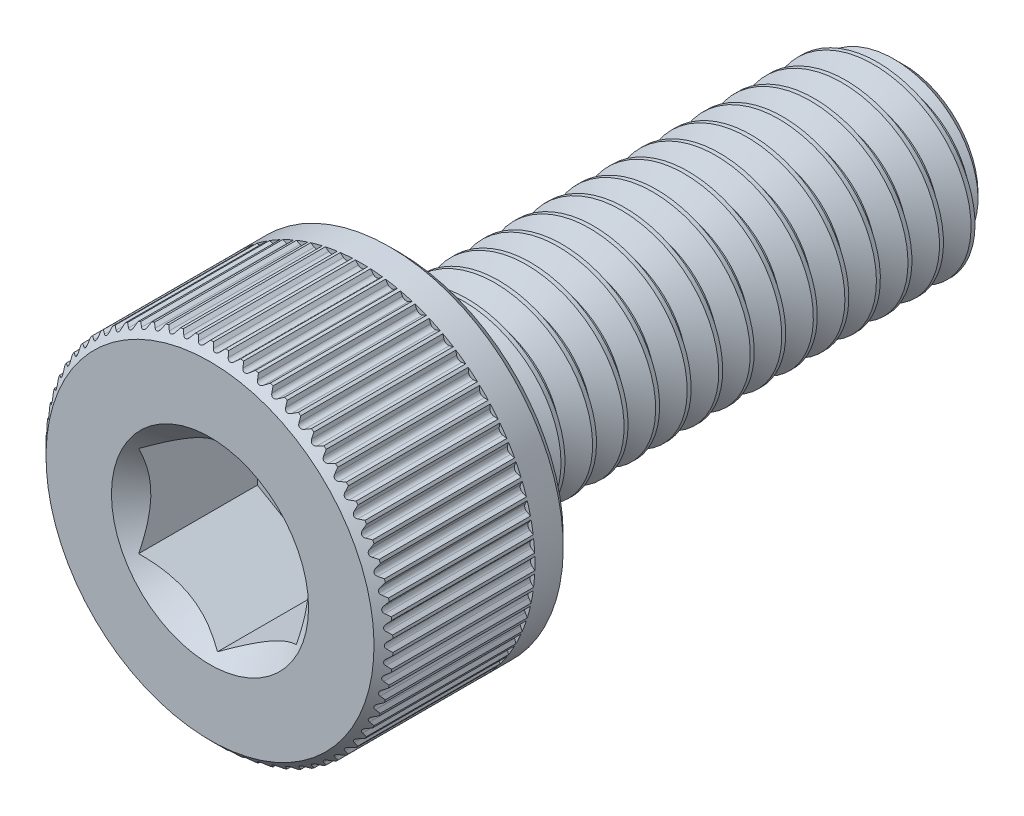
SolidWorks part; units mm, degrees
ref_plane "Front Plane" through (0, 0, 0) normal (0, 0, 1) x (1, 0, 0)
ref_plane "Top Plane" through (0, 0, 0) normal (0, 1, 0) x (1, 0, 0)
ref_plane "Right Plane" through (0, 0, 0) normal (1, 0, 0) x (0, 0, -1)
sketch "Sketch1" plane through (0, 0, 0) normal (1, 0, 0) x (0, 0, -1)
  line L0 (-5.5, 0) -> (5.5, 0) construction
  line L1 (5.5, 0) -> (5.5, 1.1752) construction
  line L2 (5.5, 1.1752) -> (5.1752, 1.5) construction
  line L3 (5.1752, 1.5) -> (5.125, 1.5) construction
  line L4 (5.125, 1.5) -> (-2.5, 1.5) construction
  line L5 (-2.5, 1.5) -> (-2.5, 2.75) construction
  line L6 (-2.5, 2.75) -> (-5.5, 2.75) construction
  line L7 (-5.5, 2.75) -> (-5.5, 0) construction
  line L8 (5.5, 1.1752) -> (5.5, 1.5) construction
  line L9 (5.4688, 1.5541) -> (5.7188, 1.1211) construction
  line L10 (5.7188, 1.1211) -> (5.9688, 1.5541) construction
  line L11 (5.9688, 1.5541) -> (5.4688, 1.5541) construction
  line L12 (5.7188, 1.5541) -> (5.7188, 1.5) construction
  line L13 (5.7188, 1.1211) -> (5.7188, 1.1752) construction
  line L14 (5.6875, 1.1752) -> (5.75, 1.1752) construction
  line L15 (5.5, 1.5) -> (5.9375, 1.5) construction
  line L16 (5.4844, 1.5271) -> (5.9531, 1.5271) construction
  line L17 (5.5, 0) -> (5.5, -1.5) construction
  line L18 (-2.65, 2.75) -> (-2.5, 2.6) construction
  line L19 (-5.35, 2.75) -> (-5.5, 2.6) construction
  line L20 (-2.5, 1.5) -> (-2.5, 0) construction
  line L21 (-2.5, 0.75) -> (0.1667, 0.75) construction
  line L22 (0.1667, 0.75) -> (2.8333, 0.75) construction
  line L23 (2.8333, 0.75) -> (5.5, 0.75) construction
  line L24 (0.1667, 0.75) -> (0.1667, 1.5) construction
  line L25 (0.1667, 1.5) -> (0.1667, 2.75) construction
  line L26 (2.8333, 0.75) -> (2.8333, 2.75) construction
  point P0 (-5.5, 1.25)
  point P3 (4.25, 1.5)
  point P4 (0, 0)
  point P18 (2.8333, 1.5)
  point P22 (5.7188, 1.1752)
  point P24 (5.125, 1.5)
  point P25 (5.7188, 1.5)
  point P28 (5.7188, 1.5271)
  point P29 (4.25, -1.5)
  point P30 (0.1667, 1.5)
  point P31 (-4, 2.75)
  point P37 (-3.025, 2.75)
  point P38 (-5.275, 2.75)
  point P45 (0.1667, 0.75)
  point P46 (2.8333, 0.75)
  dimension "D2" = 0.0625
  dimension "D7" = 0.15
  dimension "D8" = 0.15
  dimension "D9" = 0.15
  dimension "D10" = 0.075
  dimension "D11" = 0.375
  dimension "Drive Size" = 2.5
  dimension "Head Diameter" = 5.5
  dimension "Head Height" = 3
  dimension "Thread Pitch" = 0.5
  dimension "Thread Size" = 3
  dimension "Length" = 8
  dimension "D12" = 0.375
  dimension "D4" = 1.25
  dimension "D3" = 45
sketch "Sketch2" plane through (0, 0, 0) normal (1, 0, 0) x (0, 0, -1)
  line L0 (-5.5, 0) -> (-5.5, 2.6)
  line L1 (-5.35, 2.75) -> (-2.65, 2.75)
  line L2 (-2.5, 2.6) -> (-2.5, 1.65)
  line L4 (5.1752, 1.5) -> (5.5, 1.1752)
  line L5 (5.5, 1.1752) -> (5.5, 0)
  line L6 (-2.5, 2.75) -> (-5.5, 2.75) construction
  line L7 (5.5, 0) -> (-5.5, 0)
  line L8 (-5.35, 2.75) -> (-5.5, 2.6) construction
  line L10 (-5.35, 2.75) -> (-5.5, 2.6)
  line L14 (-2.65, 2.75) -> (-2.5, 2.6) construction
  line L16 (-2.65, 2.75) -> (-2.5, 2.6)
  line L17 (-2.5, 1.5) -> (-2.5, 2.75) construction
  line L19 (-2.35, 1.5) -> (5.1752, 1.5)
  line L20 (5.125, 1.5) -> (-2.5, 1.5) construction
  arc A1 (-2.5, 1.65) -> (-2.35, 1.5) centre (-2.35, 1.65) ccw
revolve "Revolve1" add sketch "Sketch2" angle 360 about L7
sketch "Sketch3" plane through (0, 0, 5.5) normal (0, 0, 1) x (1, 0, 0)
  line L1 (1.25, -0.7217) -> (1.25, 0.7217)
  line L2 (1.25, 0.7217) -> (0, 1.4434)
  line L3 (0, 1.4434) -> (-1.25, 0.7217)
  line L4 (-1.25, 0.7217) -> (-1.25, -0.7217)
  line L5 (-1.25, -0.7217) -> (0, -1.4434)
  line L6 (0, -1.4434) -> (1.25, -0.7217)
  circle A0 centre (0, 0) radius 1.25 construction
  circle A1 centre (0, 0) radius 2.75 construction
  circle A2 centre (0, 0) radius 2.75 construction
  circle A3 centre (0, 0) radius 1.4434 construction
  point P13 (0, 0)
extrude "Cut-Extrude1" cut sketch "Sketch3" against normal offset from surface (2 mm away) 1 up to face at (0, 2.6, 2.5)
sketch "Sketch4" plane through (0, 0, 5.5) normal (0, 0, 1) x (1, 0, 0)
  circle A0 centre (0, 0) radius 1.5625
  dimension "D1" = 3.125
extrude "Cut-Extrude2" cut sketch "Sketch4" against normal up to vertex (1.5 mm away) draft 45 up to point (0, 2.75, 4)
sketch "Sketch11" plane through (0, 0, 0) normal (1, 0, 0) x (0, 0, -1)
  line L0 (-5.5, 0) -> (5.5, 0) construction
  line L1 (-5.5, 0) -> (5.5, 0) construction
  line L2 (-1, 0) -> (-1, 1.5) construction
  line L3 (5.125, 1.5) -> (-2.5, 1.5) construction
  line L4 (4, 0) -> (4, 1.5) construction
  line L6 (5.5, 1.1752) -> (5.5, 1.5) construction
  point P2 (-1, 0)
  point P3 (4, 0)
  dimension "D1" = 1.5
  dimension "D2" = 1.5
sketch "Sketch6" plane through (0, 0, -5.5) normal (0, 0, -1) x (-1, 0, 0)
  circle A0 centre (0, 0) radius 1.5
curve "Helix/Spiral1" pitch 0.5 height 8.5 radius 1.5 centre (0, 0, -5.5) axis (0, 0, 1) start towards (0, 1, 0)
sketch "Sketch10" plane through (0, 0, 0) normal (1, 0, 0) x (0, 0, -1)
  line L0 (-2.35, -2.75) -> (-2.35, 2.75)
  line L5 (-5.5, 0) -> (5.5, 0) construction
  line L6 (-2.35, 1.5) -> (-2.35, -1.5) construction
  point P3 (-2.35, 0)
split "Split1" trim tools "Sketch10" bodies to split 106 resulting bodies 114 115
sketch "Sketch7" plane through (0, 0, 0) normal (1, 0, 0) x (0, 0, -1)
  line L0 (5.4844, 1.5271) -> (5.9531, 1.5271)
  line L1 (5.9531, 1.5271) -> (5.75, 1.1752)
  line L2 (5.75, 1.1752) -> (5.6875, 1.1752)
  line L3 (5.6875, 1.1752) -> (5.4844, 1.5271)
sweep "Cut-Sweep1" cut profiles "Sketch7" path "Helix/Spiral1" align with end faces yes
sketch "Sketch8" plane through (0, 0, 0) normal (1, 0, 0) x (0, 0, -1)
  line L0 (-2.5, 0) -> (-2.5, 1.5)
  line L1 (-2.35, -1.5) -> (-2.35, 1.5) construction
  line L2 (-2.5, 1.5) -> (-2.35, 1.5)
  line L4 (-2.35, 1.5) -> (-1.484, 0)
  line L5 (-1.484, 0) -> (-2.5, 0)
  line L6 (5.125, 1.5) -> (-2.5, 1.5) construction
  line L7 (-5.5, 0) -> (5.5, 0) construction
  dimension "D1" = 60
revolve "Revolve2" add sketch "Sketch8" angle 360 about L5
ref_plane "Plane1" through (0, 0, 5.5) normal (0, 0, 1) x (1, 0, 0)
sketch "Sketch12" plane through (0, 0, 5.5) normal (0, 0, 1) x (1, 0, 0)
  line L0 (0, 0) -> (0.096, 2.7483) construction
  line L1 (0, 0) -> (-0.096, 2.7483) construction
  line L2 (0, 2.6812) -> (0, 2.8187) construction
  line L3 (-0.1664, 2.8187) -> (0.1664, 2.8187)
  line L4 (-0.1664, 2.8187) -> (-0.0493, 2.7017)
  line L5 (0.0493, 2.7017) -> (0.1664, 2.8187)
  circle A0 centre (0, 0) radius 2.75 construction
  arc A1 (-0.0493, 2.7017) -> (0.0493, 2.7017) centre (0, 2.751) ccw
  point P9 (0, 2.8187)
  point P13 (0, 2.75)
  dimension "D1" = 4
  dimension "D2" = 0.0688
extrude "Cut-Extrude3" cut sketch "Sketch12" against normal blind 2.4
pattern_circular "CirPattern1" count 72 over 360 about axis through (0, 0, 5.5) along (0, 0, -1) of "Cut-Extrude3"
equation "\"D2@Sketch1\" = \"Thread Pitch@Sketch1\" / 8"
equation "\"D4@Helix/Spiral1\" = \"Thread Pitch@Sketch1\""
equation "\"D7@Sketch1\" = \"Head Height@Sketch1\" * .05"
equation "\"D8@Sketch1\"=\"D7@Sketch1\""
equation "\"D9@Sketch1\"=\"D7@Sketch1\""
equation "\"D10@Sketch1\"=\"D7@Sketch1\"/2"
equation "\"D11@Sketch1\"=\"D10@Sketch1\"*5"
equation "\"D4@Sketch1\"=\"Thread Pitch@Sketch1\"*2.5"
equation "\"D12@Sketch1\"=\"Thread Pitch@Sketch1\"*.75"
equation "\"D3@Helix/Spiral1\"=\"Length@Sketch1\"+\"Thread Pitch@Sketch1\""
equation "\"D3@Sketch2\" = \"Thread Size@Sketch1\" * 0.05"
equation "\"D1@Sketch11\"=\"Length@Sketch1\"*0.1875"
equation "\"D2@Sketch11\"=\"D1@Sketch11\""
equation "\"D2@Sketch12\"=\"Head Diameter@Sketch1\"*.0125"
equation "\"D1@Cut-Extrude3\"=\"Head Height@Sketch1\"*.8"
equation "\"D1@CirPattern1\"=\"D3@CirPattern1\"/(1.25*\"D1@Sketch12\")"
equation "\"D1@Sketch4\"=\"Drive Size@Sketch1\"*1.25"
